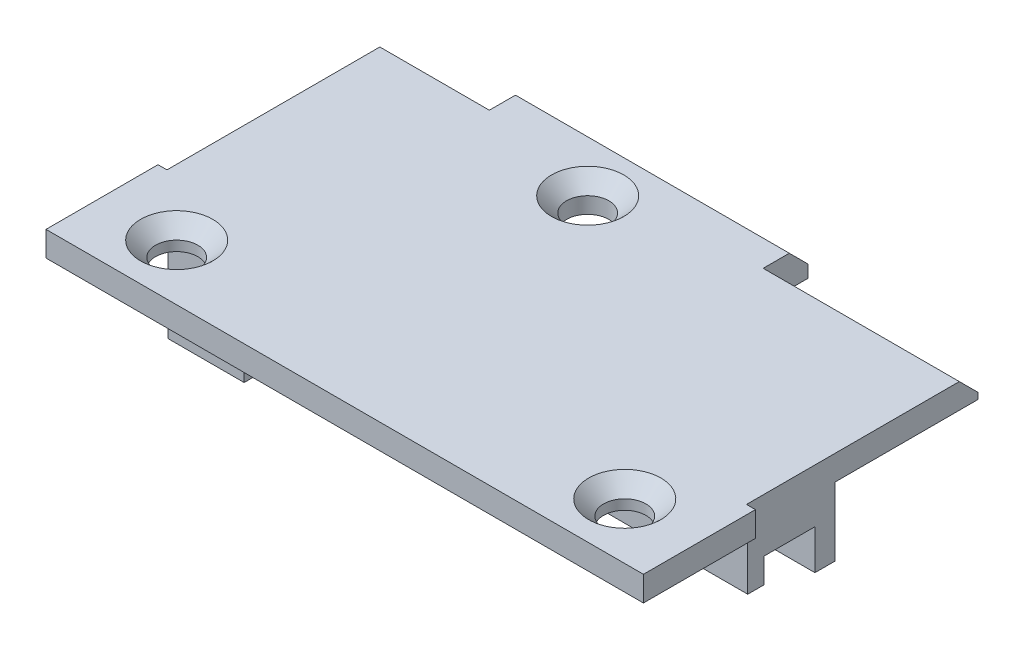
SolidWorks part; units mm, degrees
ref_plane "Front Plane" through (0, 0, 0) normal (0, 0, 1) x (1, 0, 0)
ref_plane "Top Plane" through (0, 0, 0) normal (0, 1, 0) x (1, 0, 0)
ref_plane "Right Plane" through (0, 0, 0) normal (1, 0, 0) x (0, 0, -1)
sketch "Sketch1" plane through (0, 0, 0) normal (0, 1, 0) x (1, 0, 0)
  line L0 (0, 0) -> (0, 9)
  line L1 (0, 9) -> (0.72, 9)
  line L2 (0.72, 9) -> (0.72, 27.6)
  line L3 (0.72, 27.6) -> (9.52, 27.6)
  line L4 (9.52, 27.6) -> (9.52, 29.7)
  line L5 (9.52, 29.7) -> (31.52, 29.7)
  line L6 (31.52, 29.7) -> (31.52, 27.6)
  line L7 (31.52, 27.6) -> (47.28, 27.6)
  line L8 (47.28, 27.6) -> (47.28, 9)
  line L9 (47.28, 9) -> (48, 9)
  line L10 (48, 9) -> (48, 0)
  line L11 (48, 0) -> (0, 0)
  circle A0 centre (19.42, 24.1) radius 1.7
  circle A1 centre (6, 4.5) radius 1.7
  circle A2 centre (42, 4.5) radius 1.7
  dimension "D8" = 3.4
  dimension "D1" = 48
  dimension "D2" = 9
  dimension "D3" = 0.72
  dimension "D4" = 18.6
  dimension "D5" = 2.1
  dimension "D6" = 22
  dimension "D7" = 15.76
  dimension "D9" = 24.1
  dimension "D10" = 19.42
  dimension "D11" = 4.5
  dimension "D12" = 6
  dimension "D13" = 6
  dimension "D14" = 4.5
extrude "Boss-Extrude1" add sketch "Sketch1" against normal blind 2
chamfer "Chamfer1" distance 1.5 angle 45 3 edges at (5.12, 0, -27.6) (20.52, 0, -29.7) (39.4, 0, -27.6)
chamfer "Chamfer2" distance 1.2 angle 45 3 edges at (6, 0, -2.8) (19.42, 0, -22.4) (42, 0, -2.8)
sketch "Sketch2" plane through (0, -2, 0) normal (0, -1, 0) x (1, 0, 0)
  line L0 (9.52, -28) -> (31.52, -28)
  line L1 (9.52, -29.7) -> (31.52, -29.7)
  line L2 (9.52, -29.7) -> (9.52, -28)
  line L5 (31.52, -28) -> (31.52, -29.7)
  dimension "D1" = 1.7
extrude "Boss-Extrude2" add sketch "Sketch2" along normal blind 0.5
sketch "Sketch3" plane through (0, -2, 0) normal (0, -1, 0) x (1, 0, 0)
  line L0 (19.42, -21) -> (19.42, -28) construction
  line L2 (12.42, -28) -> (12.42, -21)
  line L3 (12.42, -21) -> (26.42, -21)
  line L4 (26.42, -28) -> (26.42, -21)
  line L12 (31.52, -28) -> (9.52, -28) construction
  line L14 (12.42, -28) -> (26.42, -28)
  circle A0 centre (19.42, -24.1) radius 1.7
  circle A1 centre (19.42, -24.1) radius 1.7 construction
  dimension "D1" = 14
  dimension "D3" = 7
extrude "Boss-Extrude3" add sketch "Sketch3" along normal blind 0.5
sketch "Sketch4" plane through (0, -2, 0) normal (0, -1, 0) x (1, 0, 0)
  line L0 (0.72, -9.1) -> (47.28, -9.1)
  line L1 (47.28, -9.1) -> (47.28, -16.1)
  line L2 (47.28, -9) -> (47.28, -27.6) construction
  line L3 (47.28, -16.3) -> (44.08, -16.3) construction
  line L4 (44.08, -16.3) -> (44.08, -18.2)
  line L5 (44.08, -18.2) -> (42.26, -18.2)
  line L6 (42.26, -18.2) -> (42.26, -16)
  line L7 (42.26, -16) -> (38.56, -16)
  line L8 (38.56, -16) -> (38.56, -18.2)
  line L9 (38.56, -18.2) -> (35.18, -18.2)
  line L10 (35.18, -18.2) -> (35.18, -16)
  line L11 (35.18, -16) -> (31.48, -16)
  line L12 (31.48, -16) -> (31.48, -18.2)
  line L13 (31.48, -18.2) -> (30.28, -18.2)
  line L14 (30.28, -18.2) -> (30.28, -14.4)
  line L15 (30.28, -14.4) -> (26.6, -14.4)
  line L16 (26.6, -14.4) -> (26.6, -13.4)
  line L17 (26.6, -13.4) -> (11.4, -13.4)
  line L18 (11.4, -13.4) -> (11.4, -18.2)
  line L19 (11.4, -18.2) -> (10.02, -18.2)
  line L20 (10.02, -18.2) -> (10.02, -16)
  line L21 (10.02, -16) -> (6.32, -16)
  line L22 (6.32, -16) -> (6.32, -18.2)
  line L23 (6.32, -18.2) -> (3.72, -18.2)
  line L24 (3.72, -18.2) -> (3.72, -19.4)
  line L25 (3.72, -19.4) -> (0.72, -19.4)
  line L26 (0.72, -27.6) -> (0.72, -9) construction
  line L27 (0.72, -19.4) -> (0.72, -9.1)
  line L28 (47.28, -16.1) -> (44.08, -16.1)
  line L29 (44.08, -16.1) -> (44.08, -16.3)
  line L30 (48, -9) -> (47.28, -9) construction
  dimension "D1" = 3
  dimension "D2" = 2.6
  dimension "D3" = 3.7
  dimension "D4" = 1.38
  dimension "D5" = 15.2
  dimension "D6" = 20.68
  dimension "D7" = 3.7
  dimension "D8" = 3.7
  dimension "D9" = 3.2
  dimension "D10" = 1.2
  dimension "D11" = 3.38
  dimension "D12" = 0.1
  dimension "D13" = 1.9
  dimension "D14" = 3.8
  dimension "D15" = 1
  dimension "D16" = 4.8
  dimension "D17" = 2.2
  dimension "D18" = 1.2
  dimension "D19" = 0.2
  dimension "D20" = 7
  dimension "D21" = 5.02
  dimension "D22" = 2.2
  dimension "D23" = 2.2
extrude "Boss-Extrude4" add sketch "Sketch4" along normal blind 5.5
fillet "Fillet1" radius 0.5 12 edges at (42.26, -4.75, -18.2) (42.26, -4.75, -16) (35.18, -4.75, -18.2) (35.18, -4.75, -16) (38.56, -4.75, -16) (38.56, -4.75, -18.2) (31.48, -4.75, -16) (31.48, -4.75, -18.2) (10.02, -4.75, -18.2) (10.02, -4.75, -16) (6.32, -4.75, -16) (6.32, -4.75, -18.2)
sketch "Sketch5" plane through (0, -7.5, 0) normal (0, -1, 0) x (1, 0, 0)
  line L0 (0.72, -9) -> (0, -9) construction
  line L1 (0.72, -9.1) -> (6.82, -9.1)
  line L2 (0.72, -9.1) -> (0.72, -14.5)
  line L3 (0.72, -14.5) -> (6.82, -14.5)
  line L4 (6.82, -9.1) -> (6.82, -14.5)
  line L5 (47.28, -9.1) -> (0.72, -9.1) construction
  line L6 (0.72, -9.1) -> (0.72, -19.4) construction
  dimension "D1" = 5.5
  dimension "D2" = 6.1
extrude "Boss-Extrude5" add sketch "Sketch5" along normal blind 4.3
sketch "Sketch6" plane through (0, -7.5, 0) normal (0, -1, 0) x (1, 0, 0)
  line L0 (47.28, -16.1) -> (47.28, -9.1) construction
  line L1 (6.82, -9.1) -> (47.28, -9.1)
  line L2 (6.82, -9.1) -> (6.82, -14.5)
  line L3 (6.82, -14.5) -> (47.28, -14.5)
  line L4 (47.28, -9.1) -> (47.28, -14.5)
  line L5 (0.72, -14.5) -> (6.82, -14.5) construction
extrude "Cut-Extrude1" cut sketch "Sketch6" against normal blind 1.2
sketch "Sketch7" plane through (0, -6.3, 0) normal (0, -1, 0) x (1, 0, 0)
  line L0 (11.4, -13.4) -> (11.4, -13.12)
  line L1 (12.14, -12.15) -> (14.52, -11.4893)
  line L2 (23.64, -10.4) -> (47.28, -10.4)
  line L3 (47.28, -14.5) -> (47.28, -9.1) construction
  line L4 (47.28, -10.4) -> (47.28, -14.5)
  line L5 (47.28, -14.5) -> (26.6, -14.5)
  line L6 (26.6, -14.5) -> (26.6, -13.4)
  line L7 (26.6, -13.4) -> (11.4, -13.4)
  arc A0 (11.4, -13.12) -> (12.14, -12.15) centre (12.4, -13.1156) cw
  arc A1 (14.52, -11.4893) -> (23.64, -10.4) centre (23.1951, -45.3972) cw
  dimension "D5" = 1
  dimension "D6" = 35
  dimension "D1" = 23.64
  dimension "D2" = 4.1
  dimension "D3" = 0.28
  dimension "D4" = 2.47
  dimension "D7" = 0.97
  dimension "D8" = 0.74
  dimension "D9" = 2.38
extrude "Cut-Extrude2" cut sketch "Sketch7" against normal blind 2
sketch "Sketch8" plane through (0, -2, 0) normal (0, -1, 0) x (1, 0, 0)
  line L0 (26.42, -28) -> (26.42, -21) construction
  line L1 (12.42, -21) -> (26.42, -21)
  line L2 (12.42, -21) -> (12.42, -16)
  line L3 (12.42, -16) -> (26.42, -16)
  line L4 (26.42, -21) -> (26.42, -16)
  dimension "D1" = 5
extrude "Cut-Extrude3" cut sketch "Sketch8" against normal blind 1
